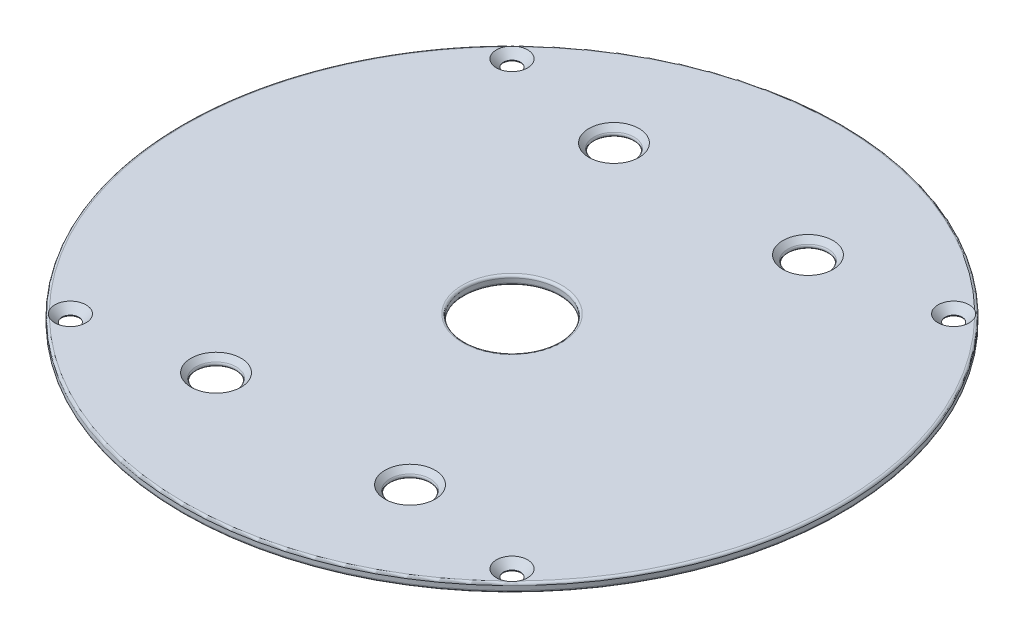
SolidWorks part; units mm, degrees
ref_plane "Front Plane" through (0, 0, 0) normal (0, 0, 1) x (1, 0, 0)
ref_plane "Top Plane" through (0, 0, 0) normal (0, 1, 0) x (1, 0, 0)
ref_plane "Right Plane" through (0, 0, 0) normal (1, 0, 0) x (0, 0, -1)
sketch "Sketch1" plane through (0, 0, 0) normal (0, 1, 0) x (1, 0, 0)
  line L0 (0, 0) -> (-46.669, 46.669) construction
  line L1 (20.5, -42.05) -> (-20.5, -42.05) construction
  line L2 (20.5, -42.05) -> (20.5, 42.05) construction
  line L3 (20.5, 42.05) -> (-20.5, 42.05) construction
  line L4 (-20.5, -42.05) -> (-20.5, 42.05) construction
  line L5 (0, 42.05) -> (0, -42.05) construction
  line L6 (20.5, 0) -> (-20.5, 0) construction
  line L7 (0, 0) -> (46.669, 46.669) construction
  line L8 (0, 0) -> (46.669, -46.669) construction
  line L9 (0, 0) -> (-46.669, -46.669) construction
  line L11 (-46.669, 46.669) -> (-42.4264, 42.4264) construction
  circle A0 centre (0, 0) radius 69.85 construction
  circle A1 centre (0, 0) radius 69.65
  circle A2 centre (-20.5, 42.05) radius 2 construction
  circle A3 centre (20.5, 42.05) radius 2 construction
  circle A4 centre (-20.5, -42.05) radius 2
  circle A5 centre (20.5, -42.05) radius 2
  circle A6 centre (-20.5, 42.05) radius 2.3
  circle A7 centre (20.5, 42.05) radius 2.3
  circle A8 centre (20.5, -42.05) radius 2.3
  circle A9 centre (-20.5, -42.05) radius 2.3
  circle A10 centre (0, 0) radius 10
  circle A11 centre (-46.669, 46.669) radius 1.5 construction
  circle A13 centre (-46.669, 46.669) radius 1.8
  circle A14 centre (46.669, 46.669) radius 1.8
  circle A15 centre (46.669, 46.669) radius 1.5 construction
  circle A16 centre (46.669, -46.669) radius 1.8
  circle A17 centre (46.669, -46.669) radius 1.5 construction
  circle A18 centre (-46.669, -46.669) radius 1.8
  circle A19 centre (-46.669, -46.669) radius 1.5 construction
  point P40 (0, 0)
  dimension "D1" = 139.7
  dimension "D5" = 4
  dimension "D7" = 20
  dimension "D9" = 3
  dimension "D3" = 84.1
  dimension "D4" = 41
  dimension "D8" = 45
  dimension "D11" = 66
  dimension "D2" = 0.2
  dimension "D6" = 0.3
  dimension "D10" = 0.3
  dimension "D12" = 4
extrude "Boss-Extrude1" add sketch "Sketch1" along normal blind 1.9 contours A1 A10 A9 A8 A7 A6 region at (-67.68, 0, 0)
chamfer "Chamfer1" distance 3 angle 45 4 edges at (-20.5, 1.9, -39.75) (20.5, 1.9, -39.75) (20.5, 1.9, 44.35) (-20.5, 1.9, 44.35)
chamfer "Chamfer3" distance 1.5 angle 45 4 edges at (-46.669, 1.9, -44.869) (46.669, 1.9, 48.469) (-46.669, 1.9, 48.469) (46.669, 1.9, -44.869)
fillet "Fillet2" radius 0.5 12 edges at (-20.5, 0, -38.65) (20.5, 0, -38.65) (20.5, 0, 45.45) (-20.5, 0, 45.45) (-46.669, 0, -44.869) (46.669, 0, -44.869) (46.669, 0, 48.469) (-46.669, 0, 48.469) (0, 0, 10) (0, 1.9, 10) (0, 0, 69.65) (0, 1.9, 69.65)
